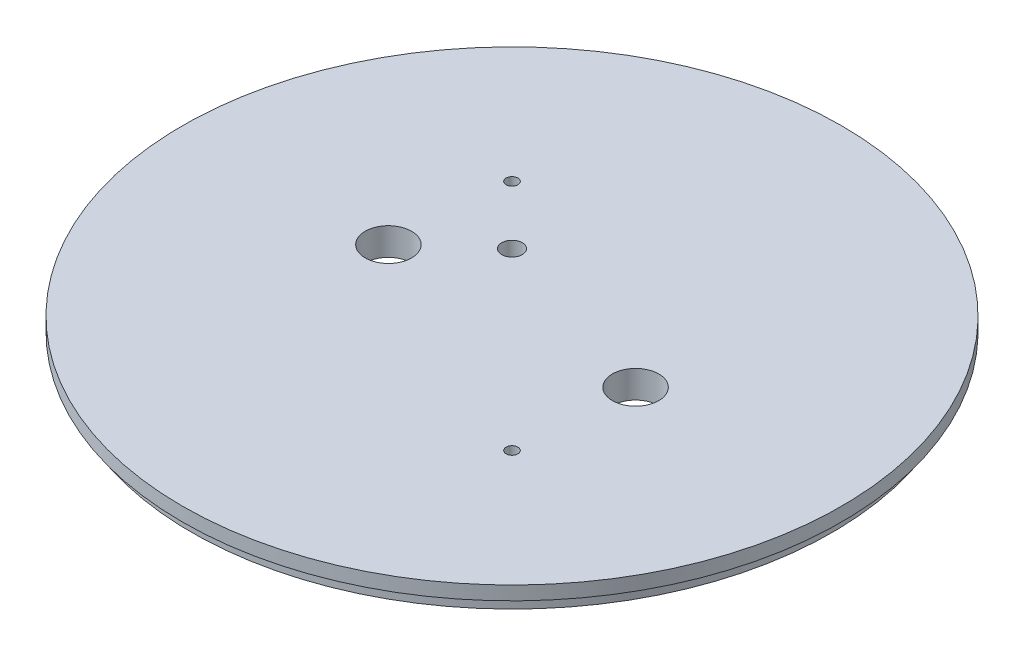
SolidWorks part; units mm, degrees
ref_plane "Front Plane" through (0, 0, 0) normal (0, 0, 1) x (1, 0, 0)
ref_plane "Top Plane" through (0, 0, 0) normal (0, 1, 0) x (1, 0, 0)
ref_plane "Right Plane" through (0, 0, 0) normal (1, 0, 0) x (0, 0, -1)
sketch "Sketch1" plane through (0, 0, 0) normal (0, 1, 0) x (1, 0, 0)
  line L0 (0, -76.2) -> (0, 76.2) construction
  line L1 (-76.2, 0) -> (76.2, 0) construction
  line L2 (-26.9408, 26.9408) -> (0, 0) construction
  line L3 (0, 56.7387) -> (0, 29.6936) construction
  line L4 (3.6407, 56.7387) -> (3.6407, 29.6936) construction
  line L5 (-3.6407, 56.7387) -> (-3.6407, 29.6936) construction
  line L6 (0, -56.7387) -> (0, -29.6936) construction
  line L7 (3.6407, -56.7387) -> (3.6407, -29.6936) construction
  line L8 (-3.6407, -56.7387) -> (-3.6407, -29.6936) construction
  line L9 (-53.8815, -53.8815) -> (54.3236, 54.3236) construction
  circle A0 centre (0, 0) radius 76.2
  circle A1 centre (0, 0) radius 3.175 construction
  circle A2 centre (28.575, 0) radius 5.3578
  circle A3 centre (-28.575, 0) radius 5.3578
  circle A4 centre (-26.9408, 26.9408) radius 1.3589
  arc A6 (3.6407, 56.7387) -> (-3.6407, 56.7387) centre (0, 56.7387) ccw construction
  arc A7 (-3.6407, 29.6936) -> (3.6407, 29.6936) centre (0, 29.6936) ccw construction
  arc A8 (3.6407, -56.7387) -> (-3.6407, -56.7387) centre (0, -56.7387) cw construction
  arc A9 (-3.6407, -29.6936) -> (3.6407, -29.6936) centre (0, -29.6936) cw construction
  circle A10 centre (26.9408, -26.9408) radius 1.3589
  circle A11 centre (-13.4704, 13.4704) radius 2.3813
  point P16 (0, 43.2162)
  point P19 (0, 0)
  point P26 (0, -43.2162)
  dimension "D1" = 152.4
  dimension "D2" = 6.35
  dimension "D3" = 10.7156
  dimension "D5" = 2.7178
  dimension "D8" = 4.7625
  dimension "D6" = 38.1
  dimension "D7" = 45
  dimension "D4" = 45
  dimension "D9" = 28.575
extrude "Boss-Extrude1" add sketch "Sketch1" along normal blind 6.35
sketch "Sketch2" plane through (0, 0, 0) normal (0, -1, 0) x (1, 0, 0)
  circle A0 centre (0, 0) radius 76.2
  circle A1 centre (0, 0) radius 74.041
  dimension "D1" = 152.4
  dimension "D2" = 148.082
extrude "Cut-Extrude1" cut sketch "Sketch2" against normal blind 3.175
sketch "Sketch3" plane through (0, 6.35, 0) normal (0, 1, 0) x (1, 0, 0)
  line L0 (0, 76.2) -> (0, -76.2) construction
  line L1 (-76.2, 0) -> (76.2, 0) construction
  line L2 (0, 34.798) -> (0, 13.97) construction
  line L3 (3.2385, 34.798) -> (3.2385, 13.97)
  line L4 (-3.2385, 34.798) -> (-3.2385, 13.97)
  line L5 (0, -34.798) -> (0, -13.97) construction
  line L6 (3.2385, -34.798) -> (3.2385, -13.97)
  line L7 (-3.2385, -34.798) -> (-3.2385, -13.97)
  circle A0 centre (0, 0) radius 76.2 construction
  arc A1 (3.2385, 34.798) -> (-3.2385, 34.798) centre (0, 34.798) ccw
  arc A2 (-3.2385, 13.97) -> (3.2385, 13.97) centre (0, 13.97) ccw
  arc A3 (3.2385, -34.798) -> (-3.2385, -34.798) centre (0, -34.798) cw
  arc A4 (-3.2385, -13.97) -> (3.2385, -13.97) centre (0, -13.97) cw
  point P7 (0, 13.97)
  point P8 (0, 34.798)
  point P12 (0, 24.384)
  point P20 (0, -24.384)
  point P25 (0, -34.798)
  point P26 (0, -13.97)
  dimension "D1" = 13.97
  dimension "D2" = 20.828
  dimension "D3" = 6.477
extrude "Cut-Extrude2" cut sketch "Sketch3" against normal blind 3.556 from offset 5.969 offset against normal yes
equation "\"leadDist\"=1.5"
equation "\"Lead_Screw_Dist\" = 2.25in"
equation "\"D9@Sketch1\"=\"Lead_Screw_Dist\"/2"
equation "\"Lead_Screw_Diam\" = (27/64)*1in"
equation "\"D3@Sketch1\"=\"Lead_Screw_Diam\""
